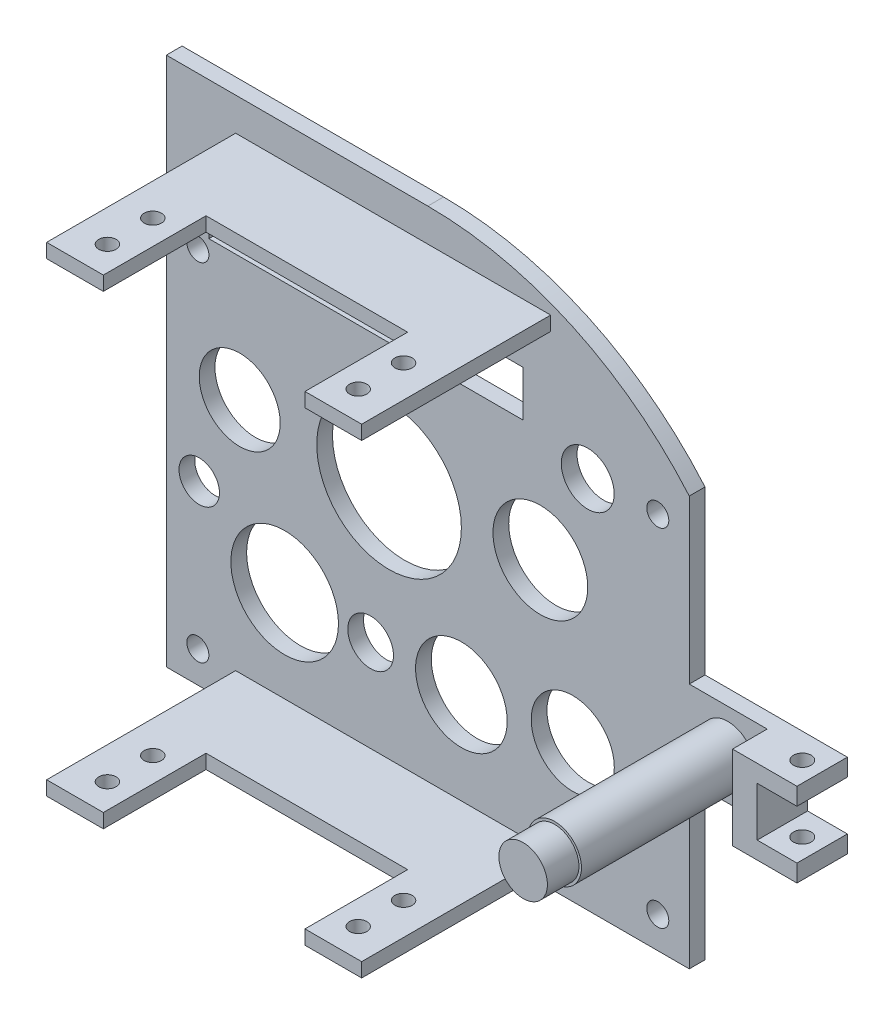
SolidWorks part; units mm, degrees
ref_plane "Front Plane" through (0, 0, 0) normal (0, 0, 1) x (1, 0, 0)
ref_plane "Top Plane" through (0, 0, 0) normal (0, 1, 0) x (1, 0, 0)
ref_plane "Right Plane" through (0, 0, 0) normal (1, 0, 0) x (0, 0, -1)
sketch "Sketch1" plane through (0, 0, 0) normal (0, 0, 1) x (1, 0, 0)
  line L0 (-14.9648, 47.7997) -> (-14.9648, -36.3102) construction
  line L1 (-56.4648, 28.6898) -> (26.5352, 28.6898) construction
  line L2 (-56.4648, 28.6898) -> (-56.4648, -36.3102)
  line L3 (-56.4648, -36.3102) -> (26.5352, -36.3102)
  line L4 (26.5352, 28.6898) -> (26.5352, 2.8428)
  line L5 (-56.4648, -3.8102) -> (26.5352, -3.8102) construction
  line L6 (42.8166, -3.8102) -> (26.5352, -3.8102) construction
  line L7 (26.5352, 2.8428) -> (49.1264, 2.8428)
  line L8 (-56.4648, 28.6898) -> (-56.4648, 47.7997)
  line L9 (26.5352, -10.4633) -> (49.1264, -10.4633)
  line L10 (49.1264, 2.8428) -> (49.1264, 0.0928)
  line L11 (49.1264, 0.0928) -> (42.8166, 0.0928)
  line L12 (42.8166, 0.0928) -> (42.8166, -7.7133)
  line L13 (49.1264, -7.7133) -> (42.8166, -7.7133)
  line L14 (49.1264, -7.7133) -> (49.1264, -10.4633)
  line L15 (26.5352, -10.4633) -> (26.5352, -36.3102)
  line L16 (-56.4648, 47.7997) -> (-14.9648, 47.7997)
  circle A0 centre (-51.4648, 23.6898) radius 1.75
  circle A1 centre (21.5352, 23.6898) radius 1.75
  circle A2 centre (21.5352, -31.3102) radius 1.75
  circle A3 centre (-51.4648, -31.3102) radius 1.75
  arc A4 (-14.9648, 47.7997) -> (26.5352, 28.6898) centre (-14.9648, -6.8169) cw
  point P25 (42.8166, -3.8102)
  dimension "D3" = 3.5
  dimension "D1" = 65
  dimension "D2" = 83
  dimension "D4" = 5
  dimension "D5" = 5
  dimension "D7" = 2.75
  dimension "D8" = 2.75
extrude "Boss-Extrude1" add sketch "Sketch1" along normal blind 2.5
sketch "Sketch2" plane through (0, 0, 2.5) normal (0, 0, 1) x (1, 0, 0)
  circle A0 centre (32.6686, -3.4744) radius 4.25
  dimension "D1" = 8.5
sketch "Sketch3" plane through (0, 0, 2.5) normal (0, 0, 1) x (1, 0, 0)
  line L0 (-56.4648, -3.8102) -> (42.8166, -3.8102) construction
  line L1 (-56.4648, 47.7997) -> (-56.4648, -36.3102) construction
  line L2 (42.8166, -7.7133) -> (42.8166, 0.0928) construction
  line L3 (-14.9648, -36.3102) -> (-14.9648, 47.7997) construction
  line L4 (-56.4648, -36.3102) -> (26.5352, -36.3102) construction
  line L5 (-51.4648, -31.3102) -> (21.5352, -31.3102) construction
  line L6 (-51.4648, 23.6898) -> (21.5352, 23.6898) construction
  line L7 (-45.4648, -31.3102) -> (4.5352, -31.3102)
  line L8 (-45.4648, -31.3102) -> (-45.4648, -33.5602)
  line L9 (-45.4648, -33.5602) -> (4.5352, -33.5602)
  line L10 (4.5352, -31.3102) -> (4.5352, -33.5602)
  line L12 (-45.4648, 29.5644) -> (0.1608, 29.5644) construction
  line L13 (-45.4648, -31.3102) -> (-45.4648, 25.9394) construction
  line L14 (-14.9648, 47.7997) -> (-56.4648, 47.7997) construction
  line L15 (-45.4648, 33.1894) -> (0.1608, 33.1894)
  line L16 (-45.4648, 40.3144) -> (4.5352, 40.3144)
  line L17 (-45.4648, 40.3144) -> (-45.4648, 42.5644)
  line L18 (-45.4648, 42.5644) -> (4.5352, 42.5644)
  line L19 (4.5352, 40.3144) -> (4.5352, 42.5644)
  line L21 (-45.4648, 25.9394) -> (0.1608, 25.9394)
  line L22 (0.1608, 33.1894) -> (0.1608, 25.9394)
  line L23 (-45.4648, 33.1894) -> (-49.7136, 33.1894)
  line L24 (-49.7136, 33.1894) -> (-49.7136, 25.9394)
  line L25 (-49.7136, 25.9394) -> (-45.4648, 25.9394)
  line L26 (-45.4648, 33.1894) -> (-45.4648, 47.7997) construction
  dimension "D1" = 2.25
  dimension "D2" = 50
  dimension "D3" = 6
  dimension "D5" = 50
  dimension "D6" = 2.25
  dimension "D7" = 7.25
  dimension "D8" = 10.75
extrude "Cut-Extrude1" cut sketch "Sketch3" against normal blind 72.5 contours L15 L22 L21 L25 L24 L23
extrude "Boss-Extrude2" add sketch "Sketch3<3>" along normal blind 30 contours L18 L19 L16 L17 | L7 L10 L9 L8
sketch "Sketch3<3>" plane through (0, 0, 2.5) normal (0, 0, 1) x (1, 0, 0) same geometry as "Sketch3"
sketch "Sketch6" plane through (0, -33.5602, 0) normal (0, -1, 0) x (1, 0, 0)
  line L0 (-20.4648, 32.5) -> (-20.4648, 2.5) construction
  line L1 (-45.4648, 32.5) -> (4.5352, 32.5) construction
  line L2 (-45.4648, 2.5) -> (4.5352, 2.5) construction
  line L3 (-45.4648, 17.5) -> (4.5352, 17.5) construction
  line L4 (-45.4648, 32.5) -> (-45.4648, 2.5) construction
  line L5 (4.5352, 32.5) -> (4.5352, 2.5) construction
  line L6 (-4.4648, 32.5) -> (-36.4648, 32.5)
  line L7 (-36.4648, 32.5) -> (-36.4648, 16.2)
  line L8 (-4.4648, 32.5) -> (-4.4648, 16.2)
  line L9 (-36.4648, 16.2) -> (-4.4648, 16.2)
  line L10 (-40.3648, 32.5) -> (-40.3648, 2.5) construction
  line L11 (-0.5648, 32.5) -> (-0.5648, 2.5) construction
  circle A0 centre (-40.3648, 27.95) radius 1.375
  circle A1 centre (-40.3648, 20.75) radius 1.375
  circle A2 centre (-0.5648, 20.75) radius 1.375
  circle A3 centre (-0.5648, 27.95) radius 1.375
  dimension "D4" = 2.75
  dimension "D6" = 2.75
  dimension "D1" = 16
  dimension "D2" = 16.3
  dimension "D3" = 3.9
  dimension "D5" = 4.55
  dimension "D7" = 7.2
extrude "Cut-Extrude2" cut sketch "Sketch6" against normal through all
extrude "Boss-Extrude4" add sketch "Sketch2" along normal blind 27.5
sketch "Sketch7" plane through (0, 0, 30) normal (0, 0, 1) x (1, 0, 0)
  circle A0 centre (32.6686, -3.4744) radius 3.85
  dimension "D1" = 7.7
extrude "Boss-Extrude5" add sketch "Sketch7" along normal blind 5
sketch "Sketch8" plane through (0, 0, 2.5) normal (0, 0, 1) x (1, 0, 0)
  line L0 (49.1264, 2.8428) -> (38.9014, 2.8428)
  line L1 (49.1264, 2.8428) -> (26.5352, 2.8428) construction
  line L2 (38.9014, 2.8428) -> (38.9014, -10.4633)
  line L3 (26.5352, -10.4633) -> (49.1264, -10.4633) construction
  line L4 (38.9014, -10.4633) -> (49.1264, -10.4633)
  line L5 (49.1264, -10.4633) -> (49.1264, -7.7133)
  line L6 (49.1264, -7.7133) -> (42.8166, -7.7133)
  line L7 (42.8166, -7.7133) -> (42.8166, 0.0928)
  line L8 (42.8166, 0.0928) -> (49.1264, 0.0928)
  line L9 (49.1264, 0.0928) -> (49.1264, 2.8428) construction
  line L10 (49.1264, 0.0928) -> (49.1264, 2.8428)
extrude "Boss-Extrude6" add sketch "Sketch8" along normal blind 5.5
sketch "Sketch10" plane through (0, 0.0928, 0) normal (0, -1, 0) x (1, 0, 0)
  line L0 (45.9715, 8) -> (45.9715, 0) construction
  line L1 (42.8166, 8) -> (49.1264, 8) construction
  line L2 (42.8166, 0) -> (49.1264, 0) construction
  line L3 (49.1264, 4) -> (42.8166, 4) construction
  line L4 (49.1264, 8) -> (49.1264, 0) construction
  line L5 (42.8166, 8) -> (42.8166, 0) construction
  circle A0 centre (45.9715, 4) radius 1.4
  dimension "D1" = 2.8
extrude "Cut-Extrude3" cut sketch "Sketch10" against normal up to surface and the other way up to surface up to face at (38.1877, 2.8428, 3.5) other way up to face at (38.1877, -10.4633, 3.5)
sketch "Sketch11" plane through (0, 0, 2.5) normal (0, 0, 1) x (1, 0, 0)
  circle A0 centre (-37.6855, -16.7055) radius 8.5399
  circle A1 centre (-21.1178, 6.2385) radius 11.48
  circle A2 centre (-9.6377, -16.7055) radius 7.2721
  circle A3 centre (2.8986, 8.0877) radius 7.5198
  circle A4 centre (8.0409, -14.5661) radius 6.5957
  circle A5 centre (-44.8189, 6.2385) radius 6.4279
  circle A6 centre (10.4184, 23.0179) radius 4.1974
  circle A7 centre (-24.0418, -16.7055) radius 3.6231
  circle A8 centre (-51.2469, -8.1656) radius 3.2107
extrude "Cut-Extrude4" cut sketch "Sketch11" against normal blind 5.5
